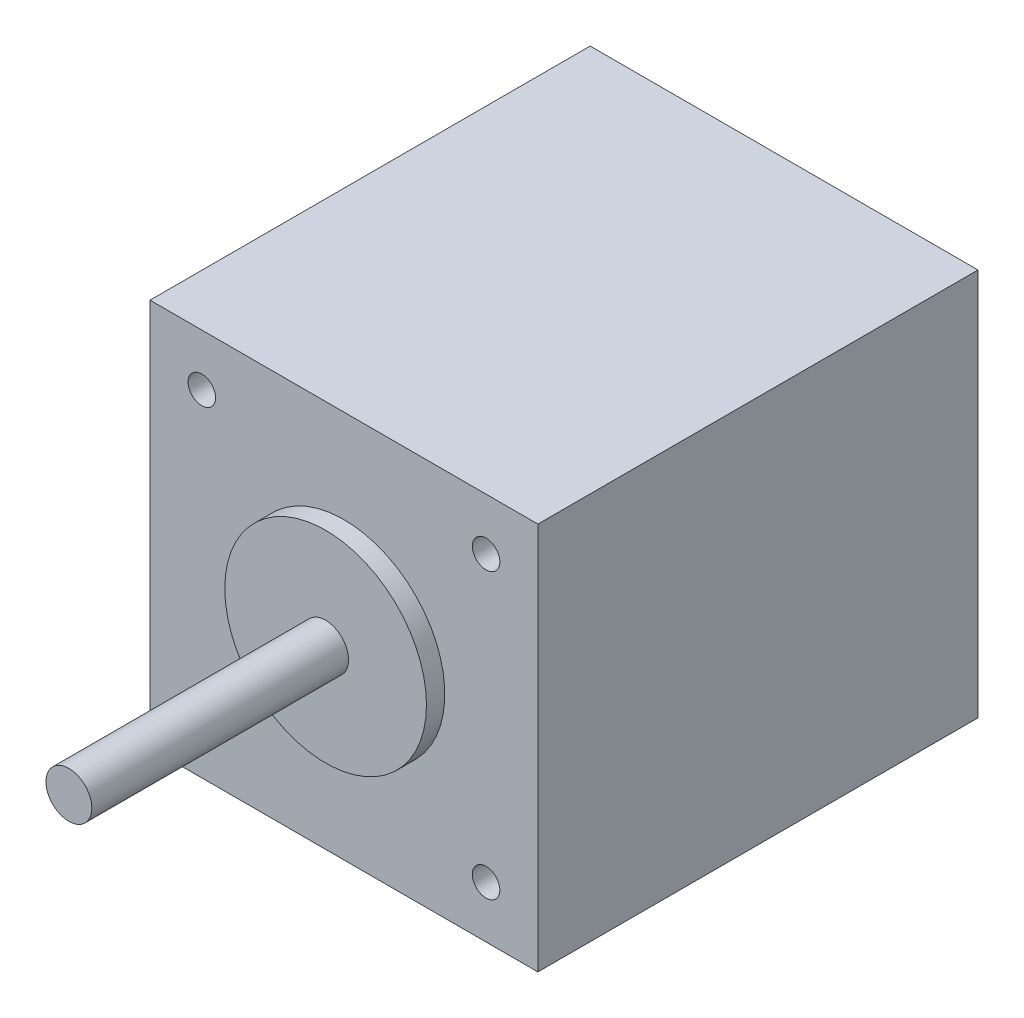
SolidWorks part; units mm, degrees
ref_plane "Спереди" through (0, 0, 0) normal (0, 0, 1) x (1, 0, 0)
ref_plane "Сверху" through (0, 0, 0) normal (0, 1, 0) x (1, 0, 0)
ref_plane "Справа" through (0, 0, 0) normal (1, 0, 0) x (0, 0, -1)
other "Configuration Table"
sketch "Эскиз1" plane through (0, 0, 0) normal (0, 0, 1) x (1, 0, 0)
  line L1 (-21.15, -21.15) -> (21.15, -21.15)
  line L2 (-21.15, -21.15) -> (-21.15, 21.15)
  line L3 (-21.15, 21.15) -> (21.15, 21.15)
  line L4 (21.15, -21.15) -> (21.15, 21.15)
  line L5 (-21.15, -21.15) -> (21.15, 21.15) construction
  line L6 (-21.15, 21.15) -> (21.15, -21.15) construction
  point P0 (0, 0)
  dimension "D1" = 42.3
  dimension "D2" = 42.3
extrude "Корпус" add sketch "Эскиз1" along normal blind 48
sketch "Эскиз2" plane through (0, 0, 0) normal (0, 0, 1) x (1, 0, 0)
  circle A0 centre (0, 0) radius 2.5
extrude "Вал_ПРЕДВ" add sketch "Эскиз2" along normal blind 78
sketch "Эскиз3" plane through (0, 0, 0) normal (0, 0, 1) x (1, 0, 0)
  circle A0 centre (0, 0) radius 11
  dimension "D1" = 22
extrude "Буртик_ПРЕДВ" add sketch "Эскиз3" along normal blind 50
sketch "Эскиз4" plane through (0, 0, 0) normal (0, 0, 1) x (1, 0, 0)
  circle A0 centre (0, 0) radius 8
  dimension "D1" = 16
sketch "Эскиз5" plane through (0, 0, 0) normal (0, 0, 1) x (1, 0, 0)
  circle A0 centre (-15.5, -15.5) radius 1.5
  circle A1 centre (-15.5, 15.5) radius 1.5
  circle A2 centre (15.5, -15.5) radius 1.5
  circle A3 centre (15.5, 15.5) radius 1.5
  dimension "D2" = 3
  dimension "D3" = 3
  dimension "D4" = 3
extrude "Крепеж_М3_ПРЕДВ" cut sketch "Эскиз5" against normal blind 4.5 from offset 48
equation "\"Мотор X ширина корпуса\"= 42.3"
equation "\"Мотор X высота корпуса\"= 42.3"
equation "\"Мотор X длина корпуса\"= 40"
equation "\"Мотор X вылет вала\"= 19.8"
equation "\"Мотор Y ширина корпуса\"= 42.3"
equation "\"Мотор Y высота корпуса\"= 42.3"
equation "\"Мотор Y длина корпуса\"= 48"
equation "\"Мотор Y вылет вала\"= 30"
equation "\"Мотор Z ширина корпуса\"= 42"
equation "\"Мотор Z высота корпуса\"= 42"
equation "\"Мотор Z длина корпуса\"= 40"
equation "\"Мотор Z вылет вала\"= 23"
equation "\"Мотор диаметр вала ПРЕДВ\"= 5"
equation "\"Мотор шаг крепления ПРЕДВ\"= 31"
equation "\"Мотор диаметр отверстий ПРЕДВ\"= 3"
equation "\"Мотор глубина отверстий ПРЕДВ\"= 4.5"
equation "\"Мотор диаметр буртика ПРЕДВ\"= 22"
equation "\"Мотор высота буртика ПРЕДВ\"= 2"
equation "\"Мотор диаметр шкива ПРЕДВ\"= 16"
equation "\"Мотор длина шкива ПРЕДВ\"= 12"
equation "\"Мотор отступ шкива ПРЕДВ\"= 5"
equation "\"Мотор X шаг градусов\"= 1.8"
equation "\"Мотор Y шаг градусов\"= 1.8"
equation "\"Мотор Z шаг градусов\"= 1.8"
equation "\"Мотор Y диаметр ротора\"= 25.78"
equation "\"D1@Эскиз1\" = \"Мотор Y ширина корпуса\""
equation "\"D1@Корпус\" = \"Мотор Y длина корпуса\""
equation "\"D1@Эскиз2\" = \"Мотор диаметр вала ПРЕДВ\""
equation "\"D1@Вал_ПРЕДВ\" = \"Мотор Y длина корпуса\" + \"Мотор Y вылет вала\""
equation "\"D1@Эскиз3\" = \"Мотор диаметр буртика ПРЕДВ\""
equation "\"D1@Буртик_ПРЕДВ\" = \"Мотор Y длина корпуса\" + \"Мотор высота буртика ПРЕДВ\""
equation "\"D1@Эскиз4\" = \"Мотор диаметр шкива ПРЕДВ\""
equation "\"D1@Эскиз5\" = \"Мотор диаметр отверстий ПРЕДВ\""
equation "\"D2@Эскиз5\" = \"Мотор диаметр отверстий ПРЕДВ\""
equation "\"D3@Эскиз5\" = \"Мотор диаметр отверстий ПРЕДВ\""
equation "\"D4@Эскиз5\" = \"Мотор диаметр отверстий ПРЕДВ\""
equation "\"D1@Крепеж_М3_ПРЕДВ\" = \"Мотор глубина отверстий ПРЕДВ\""
equation "\"D19@Крепеж_М3_ПРЕДВ\" = \"Мотор Y длина корпуса\""
equation "\"Ширина груза\"= 420"
equation "\"Глубина груза\"= 490"
equation "\"Высота груза\"= 297"
equation "\"Ширина ячейки\"= \"Ширина груза\" + 10"
equation "\"Глубина ячейки\"= \"Глубина груза\" + 10"
equation "\"Высота ячейки\"= \"Высота груза\" + 10 + 13"
equation "\"Колво ячеек ширина\"= 2"
equation "\"Колво ячеек высота\"= 2"
equation "\"Толщина стенки\" = \"Толщина тонких панелей\""
equation "\"Крепление дверцы\"= 5 "
equation "\"Ширина рейки\"= \"Толщина шестерни\""
equation "\"Высота рейки\"= 20"
equation "\"Высота пола\" = 2*\"Толщина тонких панелей\""
equation "\"Колво полозьев\"= 5"
equation "\"Отступ рейки\"= 20"
equation "\"Глубина каретки\"= \"Глубина ячейки\" + 30 + \"Мотор Y высота корпуса\" + 20"
equation "\"Отступ шпильки\"= 26"
equation "\"Диаметр шпильки\"= 5"
equation "\"Длинна шпильки\" = (\"Высота ячейки\"+\"Толщина горизонтальных плит\"+\"Высота пола\")*\"Колво ячеек высота\"+2*(\"Толщина горизонтальных плит\"+\"Отступ рейки\")"
equation "\"Ширина пластины\"= 50  "
equation "\"Высота зона выгрузки\"= \"Высота ячейки\" * 2 + \"Толщина стенки\" * 2"
equation "\"Колво выгрузки\"= 1"
equation "\"Отступ крепления мотора фиксации\" = (\"Ширина пластины\"+20-\"Толщина вертикальных стенок\")/2"
equation "\"Ширина ячейки выгрузки\" = \"Ширина ячейки\"+\"Толщина вертикальных стенок\"+2*\"Отступ крепления мотора фиксации\""
equation "\"Длинна рейки\" = (\"Ширина ячейки\"+\"Толщина вертикальных стенок\"+\"Крепление дверцы\")*\"Колво ячеек ширина\"+\"Ширина ячейки выгрузки\"*\"Колво выгрузки\"+\"Толщина вертикальных стенок\"+2*\"Отступ крепления мотора фиксации\"-\"Крепление дверцы\"*\"Колво ячеек ширина\""
equation "\"Толщина шестерни\"= 10"
equation "\"Толщина тонких панелей\"= 6"
equation "\"Толщина вертикальных стенок\"= 18"
equation "\"Толщина горизонтальных плит\"= 18"
equation "\"Базовая высота корпуса\"= (\"Высота ячейки\"+\"Толщина тонких панелей\"+\"Высота пола\")*\"Колво ячеек высота\"+6*\"Толщина тонких панелей\"+\"Мотор X ширина корпуса\"+\"Мотор Y ширина корпуса\"+75"
equation "\"Высота корпуса\"= (\"Высота ячейки\"+\"Толщина горизонтальных плит\"+\"Высота пола\")*\"Колво ячеек высота\"+2*\"Толщина горизонтальных плит\"+4*\"Толщина тонких панелей\"+\"Мотор X ширина корпуса\"+\"Мотор Y ширина корпуса\"+75"
equation "\"Смещение центра корпуса\"= (\"Высота корпуса\"-\"Базовая высота корпуса\")/2-(\"Толщина горизонтальных плит\"-\"Толщина тонких панелей\")"
equation "\"Отметка пола\"= -\"Базовая высота корпуса\"/2+\"Толщина тонких панелей\""
equation "\"Отметка потолка\"= \"Отметка пола\"+\"Высота корпуса\"-2*\"Толщина горизонтальных плит\""
equation "\"Отметка верхней полки\"= \"Отметка потолка\"-(28+\"Толщина тонких панелей\")-\"Высота ячейки\"-\"Высота пола\""
equation "\"Отметка нижней полки\"= \"Отметка верхней полки\"-\"Высота ячейки\"-\"Высота пола\"-\"Толщина горизонтальных плит\""
